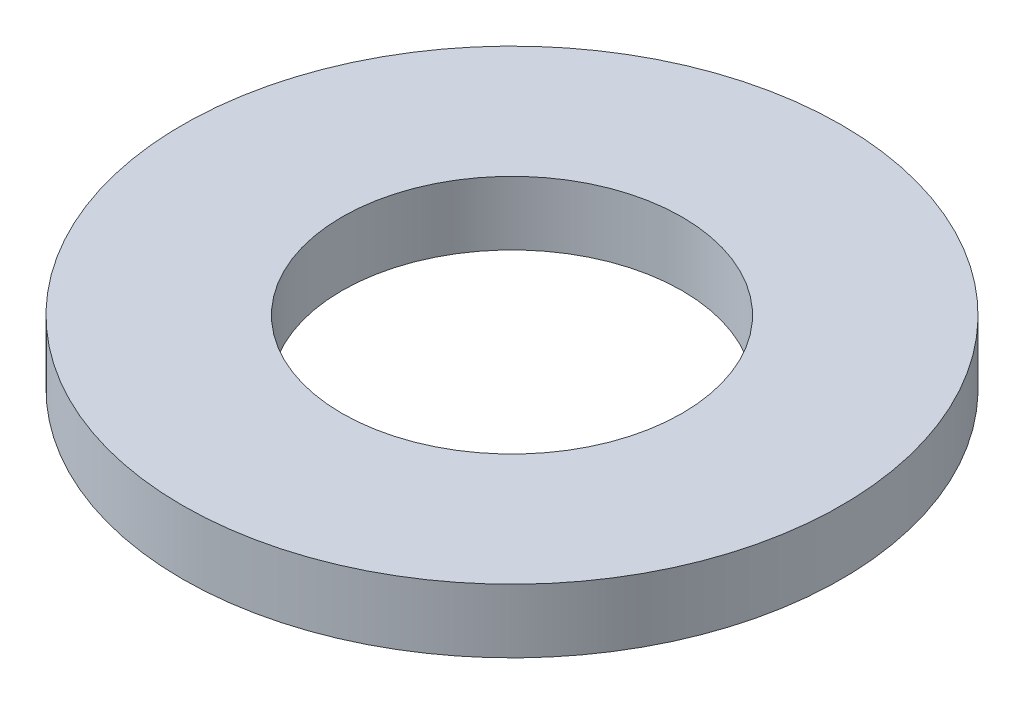
SolidWorks part; units mm, degrees
ref_plane "Front Plane" through (0, 0, 0) normal (0, 0, 1) x (1, 0, 0)
ref_plane "Top Plane" through (0, 0, 0) normal (0, 1, 0) x (1, 0, 0)
ref_plane "Right Plane" through (0, 0, 0) normal (1, 0, 0) x (0, 0, -1)
sketch "Sketch1" plane through (0, 0, 0) normal (0, 1, 0) x (1, 0, 0)
  circle A0 centre (0, 0) radius 77.5
  dimension "FLANGE_OD" = 155
extrude "Boss-Extrude1" add sketch "Sketch1" along normal blind 15
sketch "Sketch2" plane through (0, 0, 0) normal (0, 1, 0) x (1, 0, 0)
  circle A0 centre (0, 0) radius 40
  dimension "BORE_D" = 80
extrude "Cut-Extrude1" cut sketch "Sketch2" along normal through all
sketch "Sketch3" plane through (0, 15, 0) normal (0, 1, 0) x (1, 0, 0)
  circle A0 centre (0, 0) radius 27.8428 construction
  circle A1 centre (-27.8428, 0) radius 5.2778
  dimension "BOLT_D" = 10.5556
  dimension "BOLT_PCD" = 55.6856
extrude "Cut-Extrude2" cut sketch "Sketch3" against normal blind 14.168 rebuild error yes
pattern_circular "CirPattern1" count 6 over 360 rebuild error yes
